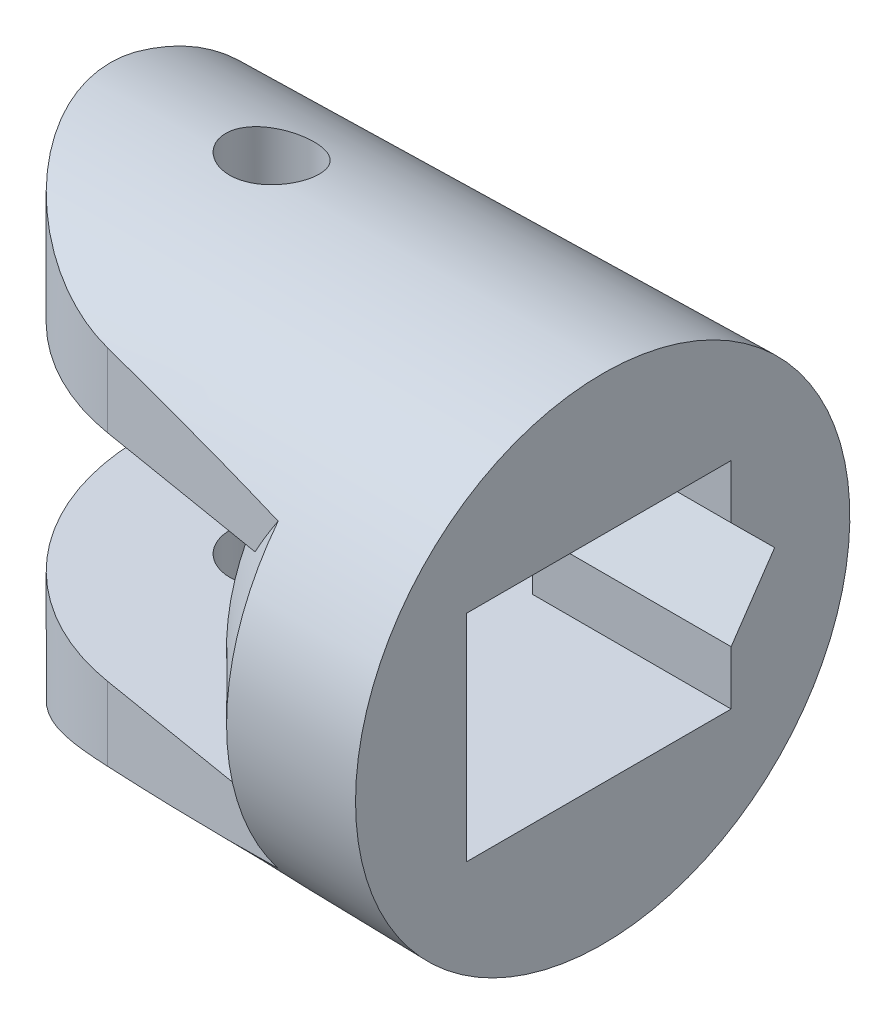
SolidWorks part; units mm, degrees
material "1060 Alloy"
ref_plane "Front Plane" through (0, 0, 0) normal (0, 0, 1) x (1, 0, 0)
ref_plane "Top Plane" through (0, 0, 0) normal (0, 1, 0) x (1, 0, 0)
ref_plane "Right Plane" through (0, 0, 0) normal (1, 0, 0) x (0, 0, -1)
sketch "Sketch1" plane through (0, 0, 0) normal (1, 0, 0) x (0, 0, -1)
  circle A0 centre (0, 0) radius 7.5
  dimension "D1" = 15
extrude "Boss-Extrude1" add sketch "Sketch1" along normal blind 18
sketch "Sketch2" plane through (0, 0, 0) normal (0, 1, 0) x (1, 0, 0)
  line L0 (10, 8.7855) -> (10, 5.5)
  line L1 (-2.6, 8.7855) -> (10, 8.7855)
  line L2 (-2.6, 8.7855) -> (-2.6, -12.2045)
  line L3 (-2.6, -12.2045) -> (10, -12.2045)
  line L5 (10, 5.5) -> (0, 5.5)
  line L6 (0, 7.5) -> (0, -7.5) construction
  line L7 (0, 5.5) -> (0, 2.31)
  line L8 (10, -12.2045) -> (10, -5.5)
  line L9 (10, -5.5) -> (5.85, -4.8109)
  line L10 (18, -7.5) -> (18, 7.5) construction
  line L11 (0, -7.5) -> (18, -7.5) construction
  arc A0 (5.85, -4.8109) -> (0, 2.31) centre (6.9967, 2.0946) cw
  dimension "D8" = 7
  dimension "D1" = 20.99
  dimension "D2" = 12.6
  dimension "D3" = 8
  dimension "D4" = 2
  dimension "D5" = 8
  dimension "D6" = 11
  dimension "D7" = 4.15
  dimension "D9" = 3.19
extrude "Cut-Extrude1" cut sketch "Sketch2" against normal mid plane 36 contours L9 A0 L7 L5 L0 L1 L2 L3 L8 region at (9.7552, 0, -7.1427)
sketch "Sketch3" plane through (0, 0, 0) normal (0, 1, 0) x (1, 0, 0)
  line L1 (10, -5.5) -> (-1, -5.5)
  line L2 (10, -5.5) -> (10, 5.5)
  line L3 (10, 5.5) -> (-1, 5.5)
  line L4 (-1, -5.5) -> (-1, 5.5)
  dimension "D1" = 11
  dimension "D2" = 11
extrude "Cut-Extrude2" cut sketch "Sketch3" against normal mid plane 6.5
sketch "Sketch4" plane through (0, 0, 0) normal (0, 1, 0) x (1, 0, 0)
  line L0 (18, 7.5) -> (18, 1) construction
  line L1 (18, -7.5) -> (18, 7.5) construction
  line L2 (18, 1) -> (5, 1) construction
  circle A0 centre (5, 1) radius 1.25
  dimension "D1" = 2.5
  dimension "D2" = 6.5
  dimension "D3" = 13
extrude "Cut-Extrude3" cut sketch "Sketch4" against normal through all and the other way through all
sketch "Sketch5" plane through (18, 0, 0) normal (1, 0, 0) x (0, 0, -1)
  circle A0 centre (0, 0) radius 7.5
  dimension "D1" = 15
extrude "Cut-Extrude-Thin1" cut sketch "Sketch5" against normal blind 23.25 draft 1 thin draft outward yes thin type one direction wall 10
fillet "Fillet1" radius 0.5 2 edges at (0, -3.9372, -5.5) (0, 3.9372, -5.5)
sketch "Sketch6" plane through (0, 0, 0) normal (0, 1, 0) x (1, 0, 0)
  line L1 (18, 7.5) -> (16, 7.5)
  line L2 (18, 7.5) -> (18, -7.66)
  line L3 (18, -7.66) -> (16, -7.66)
  line L4 (16, 7.5) -> (16, -7.66)
  dimension "D1" = 15.16
  dimension "D2" = 2
extrude "Cut-Extrude4" cut sketch "Sketch6" against normal mid plane 46.5
chamfer "Chamfer1" distance 2 angle 45 1 edges at (10, 0, 7.3604) first distance on face at (10, 0, 0)
chamfer "Chamfer2" distance 1 angle 45 1 edges at (10, 0, -7.3604) first distance on face at (10, 0, -2.3729)
sketch "Sketch7" plane through (16, 0, 0) normal (1, 0, 0) x (0, 0, -1)
  line L0 (3.88, 3.25) -> (3.88, 1.62)
  line L1 (-4.12, 3.25) -> (3.88, 3.25)
  line L2 (-4.12, 3.25) -> (-4.12, -3.25)
  line L3 (-4.12, -3.25) -> (3.88, -3.25)
  line L5 (3.88, 1.62) -> (5.1947, 0.3158)
  line L6 (5.1947, 0.3158) -> (3.88, -1.62)
  line L7 (3.88, -1.62) -> (3.88, -3.25)
  line L8 (-4.12, 0) -> (3.8718, 0) construction
  line L9 (3.88, 1.62) -> (3.88, -1.62) construction
  dimension "D1" = 8
  dimension "D2" = 1.36
  dimension "D3" = 1.63
  dimension "D4" = 1.63
  dimension "D5" = 100.59
  dimension "D6" = 4.12
  dimension "D7" = 2.34
  dimension "D8" = 6.5
extrude "Cut-Extrude5" cut sketch "Sketch7" against normal blind 10
